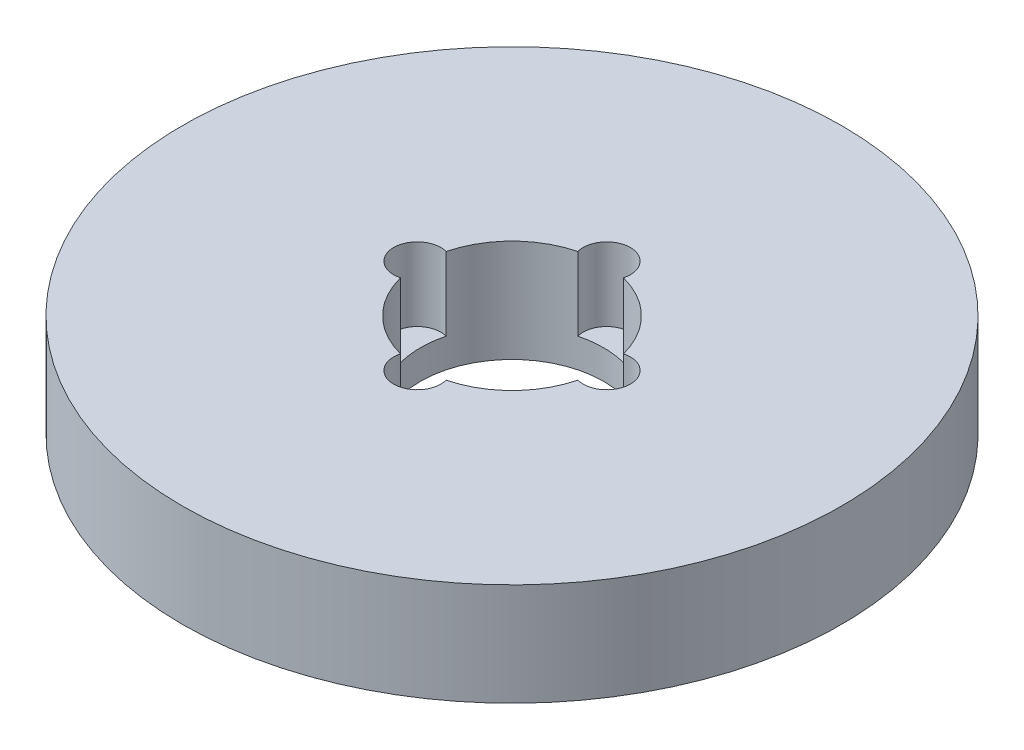
SolidWorks part; units mm, degrees
ref_plane "Front Plane" through (0, 0, 0) normal (0, 0, 1) x (1, 0, 0)
ref_plane "Top Plane" through (0, 0, 0) normal (0, 1, 0) x (1, 0, 0)
ref_plane "Right Plane" through (0, 0, 0) normal (1, 0, 0) x (0, 0, -1)
sketch "Sketch1" plane through (0, 0, 0) normal (0, 1, 0) x (1, 0, 0)
  circle A0 centre (0, 0) radius 45
  dimension "FLANGE_OD" = 90
extrude "Boss-Extrude1" add sketch "Sketch1" along normal blind 14
sketch "Sketch2" plane through (0, 0, 0) normal (0, 1, 0) x (1, 0, 0)
  circle A0 centre (0, 0) radius 12.5
  dimension "BORE_D" = 25
extrude "Cut-Extrude1" cut sketch "Sketch2" along normal through all
sketch "Sketch3" plane through (0, 14, 0) normal (0, 1, 0) x (1, 0, 0)
  circle A0 centre (0, 0) radius 12.9369 construction
  circle A1 centre (-12.9369, 0) radius 3.2233
  dimension "BOLT_D" = 6.4466
  dimension "BOLT_PCD" = 25.8737
extrude "Cut-Extrude2" cut sketch "Sketch3" against normal blind 10.0163
pattern_circular "CirPattern1" count 4 over 360 about axis through (0, 0, 0) along (0, 1, 0) of "Cut-Extrude2"
